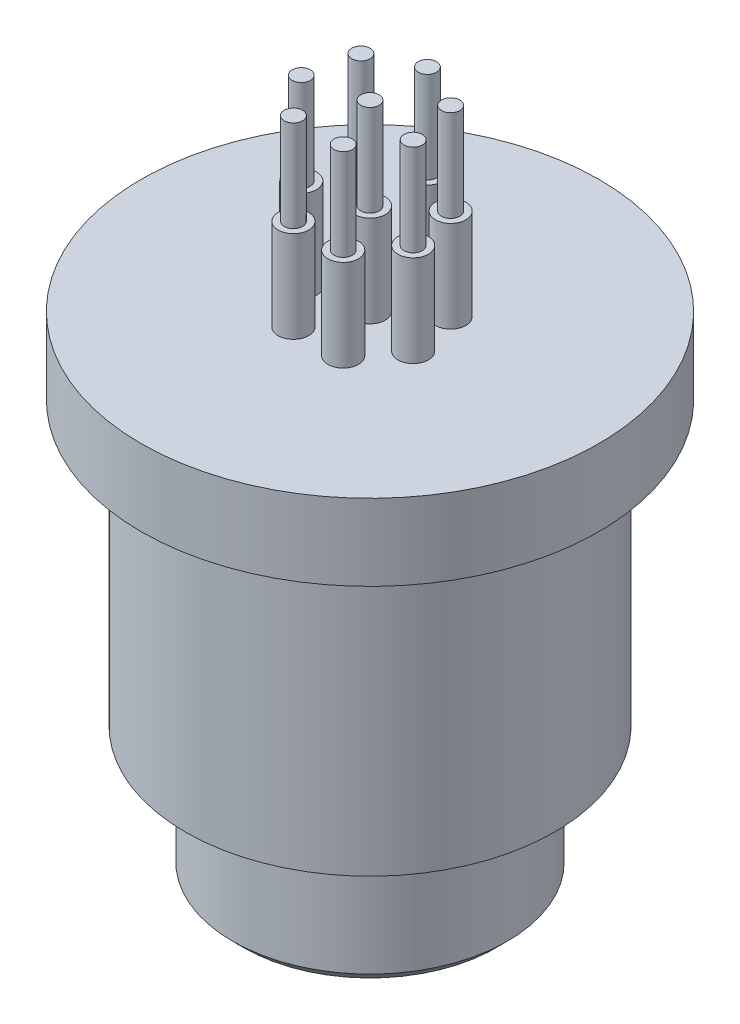
SolidWorks part; units mm, degrees
ref_plane "Front Plane" through (0, 0, 0) normal (0, 0, 1) x (1, 0, 0)
ref_plane "Top Plane" through (0, 0, 0) normal (0, 1, 0) x (1, 0, 0)
ref_plane "Right Plane" through (0, 0, 0) normal (1, 0, 0) x (0, 0, -1)
sketch "Sketch1" plane through (0, 0, 0) normal (0, 1, 0) x (1, 0, 0)
  circle A0 centre (0, 0) radius 3.5
  circle A1 centre (0, 0) radius 4.5
  dimension "D1" = 7
  dimension "D2" = 9
extrude "Boss-Extrude1" add sketch "Sketch1" along normal blind 4.25
sketch "Sketch2" plane through (0, 4.25, 0) normal (0, 1, 0) x (1, 0, 0)
  circle A1 centre (0, 0) radius 4.25
extrude "Boss-Extrude2" add sketch "Sketch2" against normal blind 1.3
sketch "Sketch3" plane through (0, 4.25, 0) normal (0, 1, 0) x (1, 0, 0)
  circle A0 centre (0, 0) radius 6.05
  dimension "D1" = 12.1
extrude "Boss-Extrude3" add sketch "Sketch3" along normal blind 9.25
sketch "Sketch6" plane through (0, 13.5, 0) normal (0, 1, 0) x (1, 0, 0)
  circle A0 centre (0, 0) radius 7.5
  dimension "D1" = 15
extrude "Boss-Extrude5" add sketch "Sketch6" along normal blind 2.5
sketch "Sketch10" plane through (0, 16, 0) normal (0, 1, 0) x (1, 0, 0)
  circle A0 centre (0, 0) radius 0.5
  circle A1 centre (0, 1.88) radius 0.5
  circle A2 centre (1.4698, 1.1722) radius 0.5
  circle A3 centre (1.8329, -0.4183) radius 0.5
  circle A4 centre (0.8157, -1.6938) radius 0.5
  circle A5 centre (-0.8157, -1.6938) radius 0.5
  circle A6 centre (-1.8329, -0.4183) radius 0.5
  circle A7 centre (-1.4698, 1.1722) radius 0.5
  point P19 (0, 0)
  dimension "D1" = 1
  dimension "D2" = 1
  dimension "D3" = 1.88
extrude "Boss-Extrude7" add sketch "Sketch10" along normal blind 3
sketch "Sketch11" plane through (0, 19, 0) normal (0, 1, 0) x (1, 0, 0)
  circle A0 centre (0, 0) radius 0.3
  circle A1 centre (0, 1.88) radius 0.3
  circle A2 centre (1.4698, 1.1722) radius 0.3
  circle A3 centre (1.8329, -0.4183) radius 0.3
  circle A4 centre (0.8157, -1.6938) radius 0.3
  circle A5 centre (-0.8157, -1.6938) radius 0.3
  circle A6 centre (-1.8329, -0.4183) radius 0.3
  circle A7 centre (-1.4698, 1.1722) radius 0.3
  dimension "D1" = 0.6
  dimension "D2" = 0.6
  dimension "D3" = 0.6
  dimension "D4" = 0.6
  dimension "D5" = 0.6
  dimension "D6" = 0.6
  dimension "D7" = 0.6
  dimension "D8" = 0.6
extrude "Boss-Extrude8" add sketch "Sketch11" along normal blind 3 contours A5
extrude "Boss-Extrude9" add sketch "Sketch11<3>" along normal blind 3
sketch "Sketch11<3>" plane through (0, 19, 0) normal (0, 1, 0) x (1, 0, 0) same geometry as "Sketch11"
chamfer "Chamfer1" distance 0.375 angle 45 1 edges at (0, 0, 4.5)
chamfer "Chamfer2" distance 0.375 angle 45 2 edges at (0, 2.95, 3.5) (0, 0, 3.5)
sketch "Sketch19" plane through (0, 0, 0) normal (0, -1, 0) x (1, 0, 0)
  circle A0 centre (0, 0) radius 3.125
  dimension "D1" = 6.25
extrude "Boss-Extrude12" add sketch "Sketch19" against normal up to next from offset 0.375 offset against normal yes
sketch "Sketch20" plane through (0, 0.375, 0) normal (0, -1, 0) x (1, 0, 0)
  circle A0 centre (0, 0) radius 0.4
  circle A1 centre (0, 1.88) radius 0.4
  circle A2 centre (1.4698, 1.1722) radius 0.4
  circle A3 centre (1.8329, -0.4183) radius 0.4
  circle A4 centre (0.8157, -1.6938) radius 0.4
  circle A5 centre (-0.8157, -1.6938) radius 0.4
  circle A6 centre (-1.8329, -0.4183) radius 0.4
  circle A7 centre (-1.4698, 1.1722) radius 0.4
  point P20 (0, 0)
  dimension "D1" = 0.8
  dimension "D2" = 0.8
  dimension "D3" = 1.88
  dimension "D4" = 7
extrude "Cut-Extrude3" cut sketch "Sketch20" against normal up to surface (3.875 mm away) up to face at (0, 4.25, 6.05)
